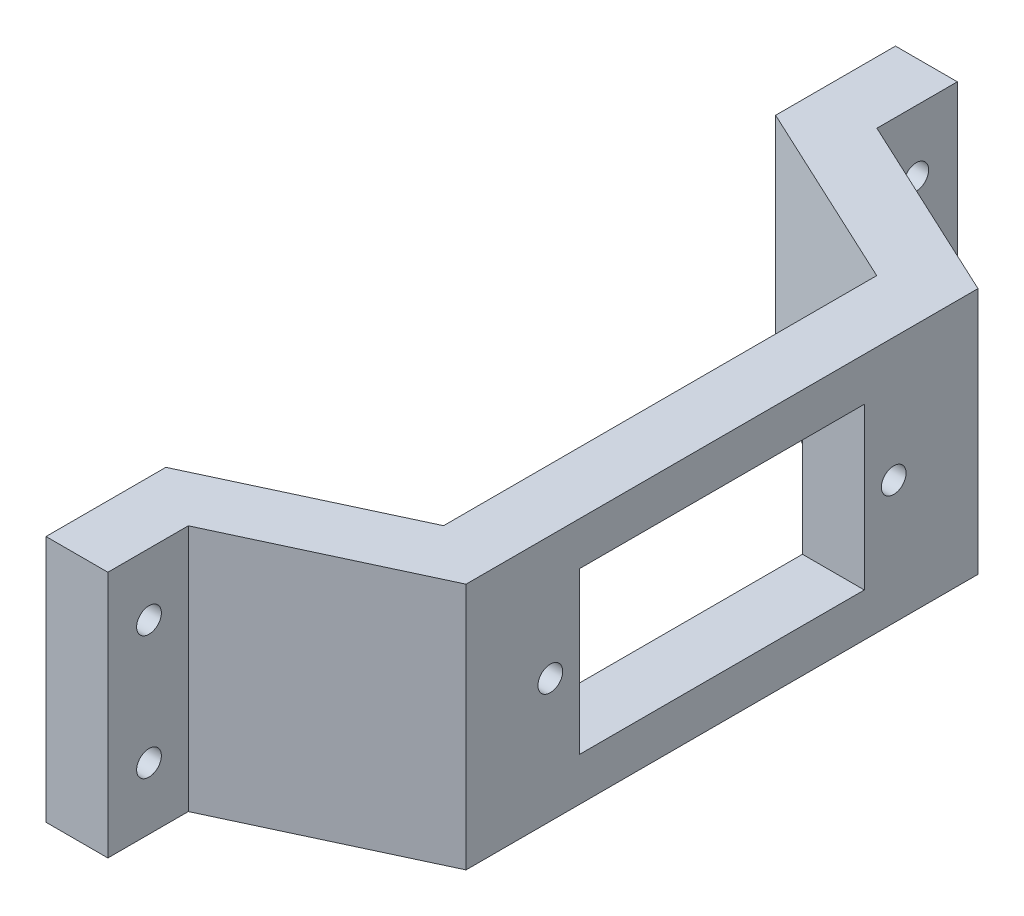
SolidWorks part; units mm, degrees
ref_plane "Front Plane" through (0, 0, 0) normal (0, 0, 1) x (1, 0, 0)
ref_plane "Top Plane" through (0, 0, 0) normal (0, 1, 0) x (1, 0, 0)
ref_plane "Right Plane" through (0, 0, 0) normal (1, 0, 0) x (0, 0, -1)
sketch "Sketch1" plane through (0, 0, 0) normal (0, 1, 0) x (1, 0, 0)
  line L0 (0, 34.3232) -> (0, 24.6379)
  line L1 (0, 24.6379) -> (15.3072, 17.5)
  line L2 (15.3072, 17.5) -> (15.3072, -17.5)
  line L3 (15.3072, -17.5) -> (0, -24.6379)
  line L4 (0, -24.6379) -> (0, -34.3232)
  line L5 (0, -34.3232) -> (5, -34.3232)
  line L6 (5, -34.3232) -> (5, -27.8232)
  line L7 (5, -27.8232) -> (20.3072, -20.6854)
  line L8 (20.3072, -20.6854) -> (20.3072, 20.6854)
  line L9 (20.3072, 20.6854) -> (5, 27.8232)
  line L10 (5, 27.8232) -> (5, 34.3232)
  line L11 (5, 34.3232) -> (0, 34.3232)
  point P14 (15.3072, 0)
  dimension "D1" = 35
  dimension "D2" = 5
  dimension "D3" = 5
  dimension "D4" = 15.3072
  dimension "D5" = 115
  dimension "D6" = 6.5
extrude "Boss-Extrude1" add sketch "Sketch1" along normal blind 10 and the other way blind 10
sketch "Sketch3" plane through (15.3072, 0, 0) normal (-1, 0, 0) x (0, 0, 1)
  line L1 (11.5, 6.5) -> (-11.5, 6.5)
  line L2 (11.5, 6.5) -> (11.5, -6.5)
  line L3 (11.5, -6.5) -> (-11.5, -6.5)
  line L4 (-11.5, 6.5) -> (-11.5, -6.5)
  line L5 (11.5, 6.5) -> (-11.5, -6.5) construction
  line L6 (11.5, -6.5) -> (-11.5, 6.5) construction
  circle A0 centre (-13.875, 0) radius 1
  circle A1 centre (13.875, 0) radius 1
  point P6 (0, 0)
  dimension "D1" = 2
  dimension "D2" = 2
  dimension "D3" = 13.875
  dimension "D4" = 13.875
  dimension "D5" = 13
  dimension "D6" = 23
extrude "Cut-Extrude1" cut sketch "Sketch3" against normal through all
sketch "Sketch5" plane through (5, 0, 0) normal (1, 0, 0) x (0, 0, -1)
  line L0 (0, 6.6224) -> (0, 0) construction
  line L1 (0, 0) -> (-6.75, 0) construction
  circle A0 centre (31, -5) radius 1
  circle A1 centre (31, 5) radius 1
  circle A2 centre (-31, 5) radius 1
  circle A3 centre (-31, -5) radius 1
  dimension "D1" = 2
  dimension "D2" = 5
  dimension "D3" = 31
extrude "Cut-Extrude2" cut sketch "Sketch5" against normal through all
